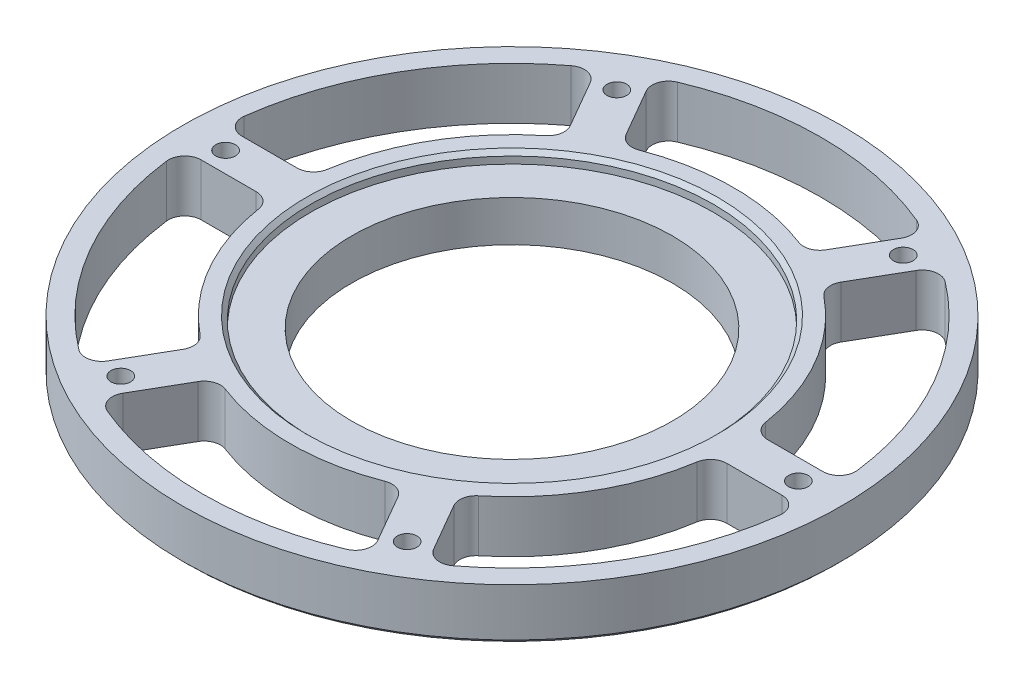
SolidWorks part; units mm, degrees
material "6061-T6 (SS)"
ref_plane "Front Plane" through (0, 0, 0) normal (0, 0, 1) x (1, 0, 0)
ref_plane "Top Plane" through (0, 0, 0) normal (0, 1, 0) x (1, 0, 0)
ref_plane "Right Plane" through (0, 0, 0) normal (1, 0, 0) x (0, 0, -1)
sketch "Sketch2" plane through (0, 0, 0) normal (1, 0, 0) x (0, 0, -1)
  line L0 (-39.2125, 0) -> (-80.55, 0)
  line L1 (-80.55, 0) -> (-80.55, 12.7)
  line L2 (-80.55, 12.7) -> (-49.2125, 12.7)
  line L3 (-49.2125, 12.7) -> (-49.2125, 10)
  line L4 (-49.2125, 10) -> (-39.2125, 10)
  line L5 (-39.2125, 10) -> (-39.2125, 0)
  dimension "D1" = 80.55
  dimension "D2" = 12.7
  dimension "D4" = 49.2125
  dimension "D5" = 10
  dimension "D3" = 10
ref_axis "Axis1" through (0, -0.635, 0) along (0, 1, 0)
revolve "Revolve1" add sketch "Sketch2" angle 360 about axis through (0, -0.635, 0) along (0, 1, 0)
hole_wizard "#12 (0.189) Diameter Hole1" positions "Sketch6" profile "Sketch7" hole size "#12" standard "ANSI Inch" end condition through all
sketch "Sketch6" plane through (0, 12.7, 0) normal (0, 1, 0) x (1, 0, 0)
  line L0 (0, 0) -> (-69.8201, 120.932) construction
  line L2 (0, 0) -> (0, 109.0908) construction
  point P0 (-35, 60.6218)
  dimension "D1" = 30
  dimension "D2" = 70
sketch "Sketch7" plane through (-35, 12.7, -60.6218) normal (1, 0, 0) x (0, 0, 1)
  line L0 (0, 0) -> (0, 12.7)
  line L1 (0, 12.7) -> (2.4003, 12.7)
  line L2 (2.4003, 12.7) -> (2.4003, 0)
  line L5 (2.4003, 0) -> (0, 0)
  line L11 (0, -6.35) -> (0, 107.95) construction
  dimension "Thru Hole Dia." = 4.8006
  dimension "Thru Hole Depth" = 12.7
pattern_circular "CirPattern3" count 6 over 360 about axis through (0, -0.635, 0) along (0, 1, 0) of "#12 (0.189) Diameter Hole1"
sketch "Sketch8" plane through (0, 12.7, 0) normal (0, 1, 0) x (1, 0, 0)
  line L0 (-33.3621, 67.7848) -> (-22.6606, 49.2493)
  line L1 (33.3621, 67.7848) -> (22.6606, 49.2493)
  line L2 (0, 0) -> (-35, 60.6218) construction
  line L4 (0, 0) -> (0, 93.9995) construction
  arc A0 (-22.6606, 49.2493) -> (22.6606, 49.2493) centre (0, 0) cw
  arc A1 (-33.3621, 67.7848) -> (33.3621, 67.7848) centre (0, 0) cw
  circle A2 centre (0, 0) radius 49.2125 construction
  circle A3 centre (0, 0) radius 80.55 construction
  dimension "D1" = 5
  dimension "D2" = 5
  dimension "D3" = 5
extrude "Cut-Extrude1" cut sketch "Sketch8" against normal through all
fillet "Fillet1" radius 4 4 edges at (33.3621, 6.35, -67.7848) (22.6606, 6.35, -49.2493) (-33.3621, 6.35, -67.7848) (-22.6606, 6.35, -49.2493)
pattern_circular "CirPattern4" count 6 over 360 about axis through (0, -0.635, 0) along (0, 1, 0) of "Cut-Extrude1", "Fillet1"
chamfer "Chamfer1" distance 1 angle 45 1 edges at (0, 12.7, -49.2125)
chamfer "Chamfer2" distance 1 angle 45 1 edges at (0, 0, -80.55)
equation "\"TubeDiameter\" = 6.500in"
equation "\"D1@Sketch2\"=(\"TubeDiameter\"-4)/2"
